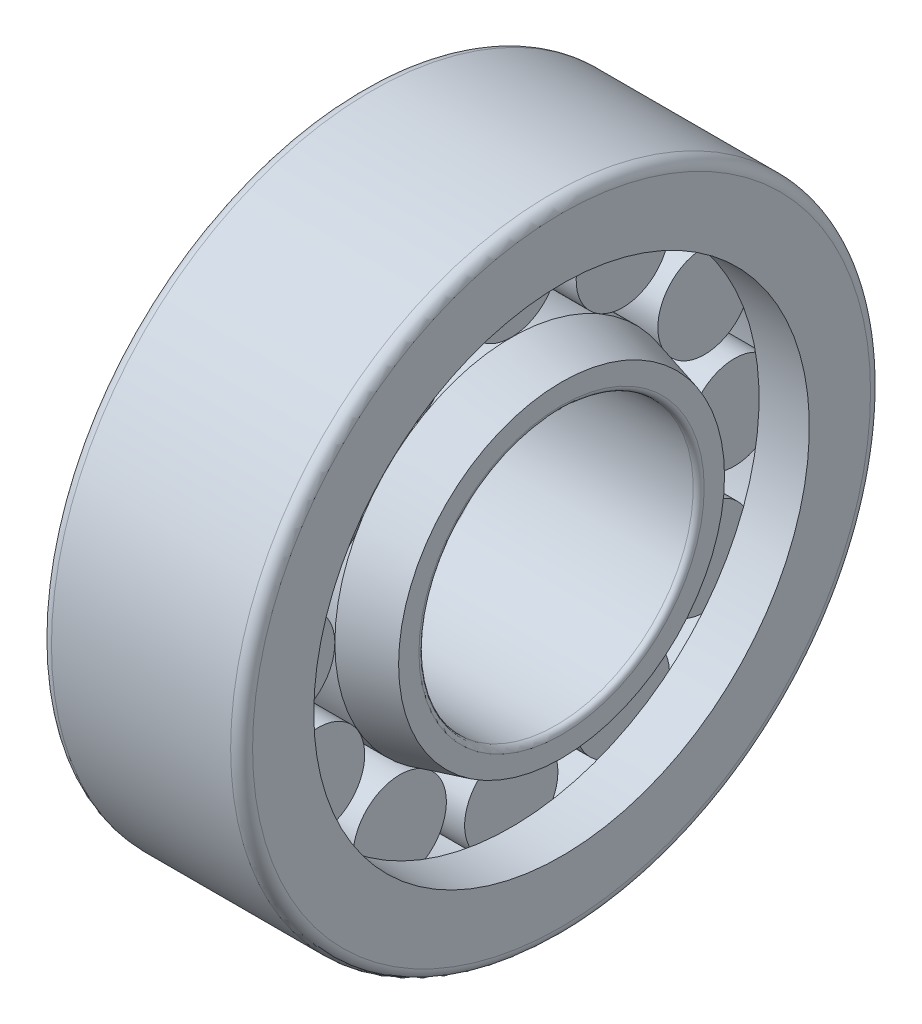
SolidWorks part; units mm, degrees
material "AISI 304"
ref_plane "基准面1" through (0, 0, 0) normal (0, 0, 1) x (1, 0, 0)
ref_plane "基准面2" through (0, 0, 0) normal (0, 1, 0) x (1, 0, 0)
ref_plane "基准面3" through (0, 0, 0) normal (1, 0, 0) x (0, 0, -1)
sketch "尺寸草图" plane through (0, 0, 0) normal (0, 0, 1) x (1, 0, 0)
  line L0 (0, 0) -> (0.3, 0)
  line L1 (0.3, 0) -> (0.9, 0)
  line L2 (0.9, 0) -> (11.9, 0)
  line L3 (11.9, 0) -> (26.9, 0)
  line L4 (26.9, 0) -> (46.2, 0)
  line L5 (46.2, 0) -> (81.2, 0)
  dimension "倒角小" = 0.3
  dimension "倒角大" = 0.6
  dimension "w" = 11
  dimension "d2" = 15
  dimension "参考FW" = 19.3
  dimension "d1" = 35
sketch "草图2" plane through (0, 0, 0) normal (0, 0, 1) x (1, 0, 0)
  line L0 (-10.0801, 0) -> (21.9267, 0) construction
  line L1 (2.75, 9.65) -> (8.25, 9.65)
  line L2 (0, 10.25) -> (2.75, 10.25)
  line L3 (0, 10.25) -> (0, 7.8)
  line L4 (0.3, 7.5) -> (10.7, 7.5)
  line L5 (11, 8.9131) -> (11, 7.8)
  line L6 (2.75, 9.65) -> (2.75, 10.25)
  line L7 (11, 8.9131) -> (8.25, 9.65)
  arc A0 (10.7, 7.5) -> (11, 7.8) centre (10.7, 7.8) ccw
  arc A1 (0, 7.8) -> (0.3, 7.5) centre (0.3, 7.8) ccw
  point P13 (11, 7.5)
  point P16 (0, 7.5)
  dimension "D1" = 0.3
  dimension "DD" = 15
  dimension "D2" = 11
  dimension "D3" = 15
  dimension "FW" = 19.3
  dimension "D4" = 20.5
revolve "基体-旋转" add sketch "草图2" angle 360 about L0
sketch "草图4" plane through (0, 0, 0) normal (0, 0, 1) x (1, 0, 0)
  line L0 (0, 0) -> (17.8006, 0) construction
  line L1 (-10.0801, 0) -> (21.9267, 0) construction
  line L2 (8.25, 13.5525) -> (11, 13.5525)
  line L3 (0.6, 17.5) -> (10.4, 17.5)
  line L4 (0, 16.9) -> (0, 13.5525)
  line L5 (0, 13.5525) -> (2.75, 13.5525)
  line L6 (11, 16.9) -> (11, 13.5525)
  line L7 (2.75, 14.7525) -> (8.25, 14.7525)
  line L8 (2.75, 14.7525) -> (2.75, 13.5525)
  line L10 (8.25, 14.7525) -> (8.25, 13.5525)
  arc A0 (10.4, 17.5) -> (11, 16.9) centre (10.4, 16.9) cw
  arc A1 (0.6, 17.5) -> (0, 16.9) centre (0.6, 16.9) ccw
  point P15 (11, 17.5)
  point P18 (0, 17.5)
  dimension "D2" = 0.6
  dimension "D1" = 29.505
  dimension "B" = 11
  dimension "D" = 35
  dimension "D3" = 1.2
revolve "凸台-旋转2" add sketch "草图4" angle 360 about L0
sketch "草图3" plane through (0, 0, 0) normal (0, 0, 1) x (1, 0, 0)
  line L1 (8.25, 13.5525) -> (8.25, -13.5525) construction
  line L3 (2.75, 14.7525) -> (8.25, 14.7525)
  line L6 (2.75, 14.7525) -> (2.75, 12.2012)
  line L7 (2.75, 12.2012) -> (8.25, 12.2012)
  line L8 (8.25, 14.7525) -> (8.25, 12.2012)
  line L9 (2.75, -14.7525) -> (2.75, 14.7525) construction
  line L10 (2.75, 14.7525) -> (2.75, 9.65) construction
  line L11 (2.75, 12.2012) -> (8.25, 12.2012) construction
  dimension "D2" = 2.5513
revolve "凸台-旋转1" add sketch "草图3" angle 360 about L7
ref_axis "基准轴1" through (-80.9, 0, 0) along (1, 0, 0)
pattern_circular "阵列(圆周)1" count 12 over 360 about axis through (-80.9, 0, 0) along (1, 0, 0) of bodies 102
